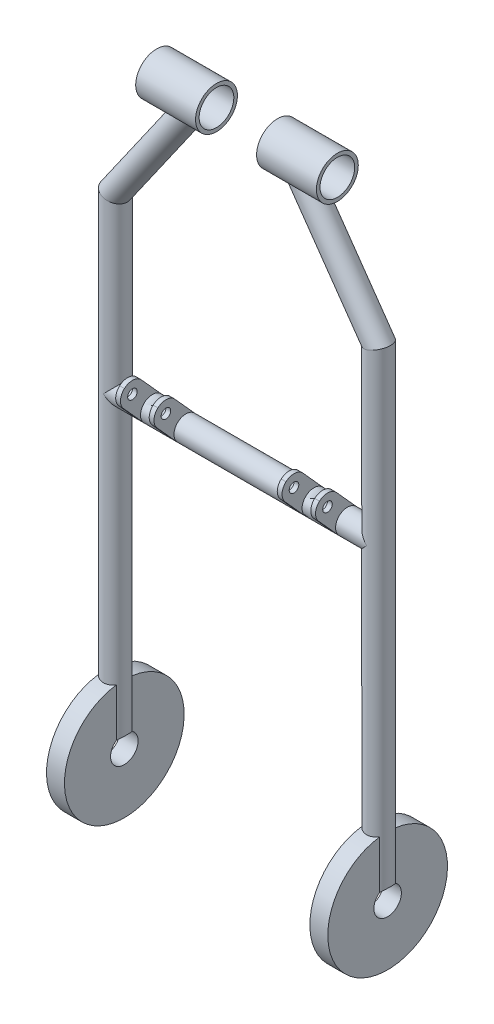
SolidWorks part; units mm, degrees
ref_plane "Alzado" through (0, 0, 0) normal (0, 0, 1) x (1, 0, 0)
ref_plane "Planta" through (0, 0, 0) normal (0, 1, 0) x (1, 0, 0)
ref_plane "Vista lateral" through (0, 0, 0) normal (1, 0, 0) x (0, 0, -1)
sketch "Croquis1" plane through (0, 0, 0) normal (1, 0, 0) x (0, 0, -1)
  circle A0 centre (0, 0) radius 17.5
  circle A1 centre (0, 0) radius 14.5
  dimension "D1" = 35
  dimension "D2" = 3
extrude "Saliente-Extruir1" add sketch "Croquis1" along normal blind 50
sketch "Croquis2" plane through (0, 0, 0) normal (0, 0, 1) x (1, 0, 0)
  line L0 (25, -17.5) -> (-34.5176, -102.5)
  line L1 (-34.5176, -102.5) -> (-34.5176, -502.5)
  line L2 (-34.5176, -102.5) -> (29.5486, -102.5) construction
  line L3 (25, 17.5) -> (25, -17.5) construction
  line L4 (50, 17.5) -> (0, 17.5) construction
  line L5 (0, -17.5) -> (50, -17.5) construction
  line L6 (0, 0) -> (50, 0) construction
  line L7 (50, -17.5) -> (50, 17.5) construction
  dimension "D1" = 85
  dimension "D2" = 400
  dimension "D3" = 55
  dimension "D4" = 64.0663
ref_plane "Plano1" through (25, -17.5, 0) normal (-0.5736, -0.8192, 0) x (0, 0, 1)
sketch "Croquis3" plane through (25, -17.5, 0) normal (-0.5736, -0.8192, 0) x (0, 0, 1)
  circle A0 centre (0, 0) radius 10
  circle A1 centre (0, 0) radius 7
  dimension "D2" = 3
  dimension "D1" = 20
sweep "Barrer1" add profiles "Croquis3" path "Croquis2"
sketch "Croquis4" plane through (50, 0, 0) normal (1, 0, 0) x (0, 0, -1)
  circle A0 centre (0, 0) radius 14.5 construction
  circle A1 centre (0, 0) radius 14.5
extrude "Cortar-Extruir1" cut sketch "Croquis4" against normal through all
sketch "Croquis5" plane through (0.0024, 0.0035, 0) normal (0.5736, 0.8192, 0) x (0.8192, -0.5736, 0)
  arc A4 (40.5164, 0) -> (26.1673, 9.0048) centre (30.5164, 0) ccw
  arc A5 (37.5164, 0) -> (28.2476, 6.6221) centre (30.5164, 0) ccw
  arc A6 (28.2476, -6.6221) -> (37.5164, 0) centre (30.5164, 0) ccw
  arc A7 (26.1673, -9.0048) -> (40.5164, 0) centre (30.5164, 0) ccw
  arc A8 (40.5164, 0) -> (26.1673, 9.0048) centre (30.5164, 0) ccw
  arc A9 (37.5164, 0) -> (28.2476, 6.6221) centre (30.5164, 0) ccw
  arc A10 (28.2476, -6.6221) -> (37.5164, 0) centre (30.5164, 0) ccw
  arc A11 (26.1673, -9.0048) -> (40.5164, 0) centre (30.5164, 0) ccw
  ellipse E2 centre (0.0061, 0) end of major axis (-30.5042, 0) minor radius 17.5 (28.2476, 6.6221) -> (26.1673, 9.0048) ccw
  ellipse E3 centre (0.0061, 0) end of major axis (-30.5042, 0) minor radius 17.5 (26.1673, -9.0048) -> (28.2476, -6.6221) ccw
  ellipse E4 centre (0.0061, 0) end of major axis (-30.5042, 0) minor radius 17.5 (28.2476, 6.6221) -> (26.1673, 9.0048) ccw
  ellipse E5 centre (0.0061, 0) end of major axis (-30.5042, 0) minor radius 17.5 (26.1673, -9.0048) -> (28.2476, -6.6221) ccw
  dimension "D1" = 0
extrude "Saliente-Extruir2" add sketch "Croquis5" along normal up to body separate body
ref_plane "Plano3" through (101, 0, 0) normal (1, 0, 0) x (0, 0, -1)
sketch "Croquis6" plane through (101, 0, 0) normal (1, 0, 0) x (0, 0, -1)
  circle A0 centre (0, 0) radius 14.5 construction
  circle A1 centre (0, 0) radius 17.5 construction
  circle A2 centre (0, 0) radius 14.5
  circle A3 centre (0, 0) radius 17.5
extrude "Saliente-Extruir3" add sketch "Croquis6" along normal blind 50 separate body
sketch "Croquis7" plane through (0, 0, 0) normal (0, 0, 1) x (1, 0, 0)
  line L0 (151, -17.5) -> (151, 17.5) construction
  line L1 (101, -17.5) -> (151, -17.5) construction
  line L2 (101, 17.5) -> (101, -17.5) construction
  line L3 (151, 17.5) -> (101, 17.5) construction
  line L4 (151, -17.5) -> (151, 17.5) construction
  line L5 (101, -17.5) -> (151, -17.5) construction
  line L6 (101, 17.5) -> (101, -17.5) construction
  line L7 (151, 17.5) -> (101, 17.5) construction
  line L8 (126, -17.5) -> (185.5176, -102.5)
  line L9 (185.5176, -102.5) -> (185.5176, -502.5)
  line L10 (185.5176, -102.5) -> (99.3833, -102.5) construction
  dimension "D1" = 85
  dimension "D2" = 400
  dimension "D3" = 86.1343
  dimension "D4" = 55
ref_plane "Plano4" through (126, -17.5, 0) normal (0.5736, -0.8192, 0) x (-0.8192, -0.5736, 0)
sketch "Croquis8" plane through (126, -17.5, 0) normal (0.5736, -0.8192, 0) x (-0.8192, -0.5736, 0)
  circle A0 centre (0, 0) radius 10
  circle A1 centre (0, 0) radius 7
  dimension "D2" = 3
  dimension "D1" = 20
sweep "Barrer2" add profiles "Croquis8" path "Croquis7"
sketch "Croquis9" plane through (49.675, -70.9433, 0) normal (-0.5736, 0.8192, 0) x (0.8192, 0.5736, 0)
  arc A2 (95.4443, 6.6221) -> (95.4443, -6.6221) centre (93.1756, 0) ccw
  arc A3 (97.5246, 9.0048) -> (97.5246, -9.0048) centre (93.1756, 0) ccw
  arc A4 (95.4443, 6.6221) -> (95.4443, -6.6221) centre (93.1756, 0) ccw
  arc A5 (97.5246, 9.0048) -> (97.5246, -9.0048) centre (93.1756, 0) ccw
  ellipse E2 centre (123.6859, 0) end of major axis (93.1756, 0) minor radius 17.5 (97.5246, 9.0048) -> (95.4443, 6.6221) ccw
  ellipse E3 centre (123.6859, 0) end of major axis (93.1756, 0) minor radius 17.5 (95.4443, -6.6221) -> (97.5246, -9.0048) ccw
  ellipse E4 centre (123.6859, 0) end of major axis (93.1756, 0) minor radius 17.5 (97.5246, 9.0048) -> (95.4443, 6.6221) ccw
  ellipse E5 centre (123.6859, 0) end of major axis (93.1756, 0) minor radius 17.5 (95.4443, -6.6221) -> (97.5246, -9.0048) ccw
  dimension "D1" = 0
extrude "Saliente-Extruir4" add sketch "Croquis9" along normal up to surface up to face at (132.5056, -16.5721, 0.0091)
sketch "Croquis10" plane through (0, 0, 0) normal (1, 0, 0) x (0, 0, -1)
  line L0 (10, -102.5) -> (10, -14.3614) construction
  line L1 (-10, -14.3614) -> (-10, -102.5) construction
  line L2 (10, -502.5) -> (10, -102.5) construction
  line L3 (-10, -102.5) -> (-10, -502.5) construction
  line L4 (10, -102.5) -> (10, -14.3614) construction
  line L5 (-10, -14.3614) -> (-10, -102.5) construction
  line L6 (10, -502.5) -> (10, -102.5) construction
  line L7 (-10, -102.5) -> (-10, -502.5) construction
  line L10 (0, -502.5) -> (0, -11.7642) construction
  circle A0 centre (0, -244.3614) radius 10
  dimension "D2" = 20
  dimension "D1" = 230
extrude "Saliente-Extruir5" add sketch "Croquis10" along normal up to surface and the other way up to surface contours A0 up to face at (195.5176, -99.347, 0) other way up to face at (-44.5176, -99.347, 0)
sketch "Croquis11" plane through (0, -502.5, 0) normal (0, -1, 0) x (1, 0, 0)
  line L0 (-34.5176, 0) -> (-44.5176, 0)
  circle A0 centre (-34.5176, 0) radius 10 construction
  circle A1 centre (-34.5176, 0) radius 10 construction
ref_plane "Plano5" through (-34.5176, -502.5, 0) normal (-1, 0, 0) x (0, 0, 1)
sketch "Croquis12" plane through (-34.5176, -502.5, 0) normal (-1, 0, 0) x (0, 0, 1)
  line L0 (-10, 0) -> (10, 0) construction
  circle A0 centre (0, 0) radius 50
  dimension "D1" = 100
extrude "Saliente-Extruir6" add sketch "Croquis12" along normal mid plane 15
chamfer "Chaflán3" distance 7 angle 45 2 edges at (-25.1635, -502.5, -3.5355) (-25.1635, -502.5, 3.5355)
chamfer "Chaflán4" distance 7 angle 45 1 edges at (-44.5176, -502.5, 0)
sketch "Croquis13" plane through (0, -502.5, 0) normal (0, -1, 0) x (1, 0, 0)
  line L0 (185.5176, 0) -> (175.5176, 0) construction
  circle A0 centre (185.5176, 0) radius 10 construction
  circle A1 centre (185.5176, 0) radius 10 construction
ref_plane "Plano6" through (185.5176, -502.5, 0) normal (-1, 0, 0) x (0, 0, 1)
sketch "Croquis14" plane through (185.5176, -502.5, 0) normal (-1, 0, 0) x (0, 0, 1)
  arc A0 (-6.6144, 49.5606) -> (6.6144, 49.5606) centre (0, 0) ccw construction
  arc A1 (-6.6144, 49.5606) -> (6.6144, 49.5606) centre (0, 0) ccw
  circle A2 centre (0, 0) radius 50
extrude "Saliente-Extruir8" add sketch "Croquis14" along normal mid plane 15 contours A2
sketch "Croquis15" plane through (151, 0, 0) normal (1, 0, 0) x (0, 0, -1)
  circle A0 centre (0, 0) radius 14.5 construction
  circle A1 centre (0, 0) radius 14.5
extrude "Cortar-Extruir2" cut sketch "Croquis15" against normal through all contours A1
ref_plane "Plano7" through (75, 0, 0) normal (1, 0, 0) x (0, 0, -1)
sketch "Croquis16" plane through (75, 0, 0) normal (1, 0, 0) x (0, 0, -1)
  line L0 (0, -244.3614) -> (-23.4196, -218.3513)
  line L1 (0, -244.3614) -> (0, -194.3614) construction
  arc A0 (-10, -244.3614) -> (10, -244.3614) centre (0, -244.3614) ccw construction
  arc A1 (10, -244.3614) -> (-10, -244.3614) centre (0, -244.3614) ccw construction
  arc A2 (-10, -244.3614) -> (10, -244.3614) centre (0, -244.3614) ccw
  arc A3 (10, -244.3614) -> (-10, -244.3614) centre (0, -244.3614) ccw
  dimension "D1" = 50
  dimension "D2" = 42
  dimension "D3" = 35
ref_plane "Plano8" through (75, -218.3513, 23.4196) normal (0, 0.7431, 0.6691) x (1, 0, 0)
sketch "Croquis17" plane through (75, -218.3513, 23.4196) normal (0, 0.7431, 0.6691) x (1, 0, 0)
  line L0 (120.5176, -172.7284) -> (120.5176, 97.0336) construction
  line L1 (-119.5176, 97.0336) -> (-119.5176, -168.0445) construction
  line L2 (120.5176, -172.7284) -> (120.5176, 97.0336) construction
  line L3 (-119.5176, 97.0336) -> (-119.5176, -168.0445) construction
  line L4 (-102.8263, -10) -> (103.8263, -10) construction
  line L5 (103.8263, 10) -> (-102.8263, 10) construction
  line L6 (-102.8263, -10) -> (103.8263, -10) construction
  line L7 (103.8263, 10) -> (-102.8263, 10) construction
  line L8 (-119.5176, 0) -> (120.5176, 0) construction
  line L9 (-82.5, 10) -> (-78.5, 10)
  line L10 (-82.5, 10) -> (-82.5, -10)
  line L11 (-82.5, -10) -> (-78.5, -10)
  line L12 (-78.5, 10) -> (-78.5, -10)
  line L13 (-82.5, 10) -> (-78.5, -10) construction
  line L14 (-82.5, -10) -> (-78.5, 10) construction
  line L15 (-50.5, 10) -> (-54.5, 10)
  line L16 (-50.5, 10) -> (-50.5, -10)
  line L17 (-50.5, -10) -> (-54.5, -10)
  line L18 (-54.5, 10) -> (-54.5, -10)
  line L19 (-50.5, 10) -> (-54.5, -10) construction
  line L20 (-50.5, -10) -> (-54.5, 10) construction
  line L29 (0, 0) -> (0, 33.4565) construction
  line L30 (0.5, 0) -> (0.5, -10) construction
  line L31 (0, 0) -> (0, 33.4565) construction
  line L32 (52.5, -10) -> (56.5, -10)
  line L33 (52.5, 10) -> (52.5, -10)
  line L34 (52.5, 10) -> (56.5, 10)
  line L35 (56.5, 10) -> (56.5, -10)
  line L36 (84.5, -10) -> (80.5, -10)
  line L37 (80.5, 10) -> (80.5, -10)
  line L38 (84.5, 10) -> (80.5, 10)
  line L39 (84.5, 10) -> (84.5, -10)
  point P12 (-80.5, 0)
  point P17 (-52.5, 0)
  point P32 (80.5, 10)
  point P33 (0, 0)
  dimension "D1" = 24
  dimension "D2" = 4
  dimension "D3" = 4
  dimension "D4" = 50.5
  dimension "D5" = 52.5
  dimension "D6" = 24
  dimension "D7" = 4
  dimension "D8" = 4
extrude "Saliente-Extruir10" add sketch "Croquis17" against normal up to body separate body contours L12 L11 L10 L9 | L16 L17 L18 L15 | L35 L34 L33 L32 | L36 L37 L38 L39
fillet "Redondeo1" radius 10 8 edges at (157.5, -225.0426, 30.851) (157.5, -211.66, 15.9881) (129.5, -225.0426, 30.851) (129.5, -211.66, 15.9881) (-5.5, -225.0426, 30.851) (-5.5, -211.66, 15.9881) (22.5, -211.66, 15.9881) (22.5, -225.0426, 30.851)
sketch "Croquis18" plane through (-7.5, 0, 0) normal (-1, 0, 0) x (0, 0, 1)
  circle A0 centre (16.7283, -225.7828) radius 4
  dimension "D1" = 8
extrude "Cortar-Extruir3" cut sketch "Croquis18" against normal through all
ref_plane "Plano9" through (-52.0176, 0, 0) normal (-1, 0, 0) x (0, 0, 1)
sketch "Croquis19" plane through (-52.0176, 0, 0) normal (-1, 0, 0) x (0, 0, 1)
  line L0 (-10, -502.5) -> (10, -502.5) construction
  circle A0 centre (0, -502.5) radius 50 construction
  arc A1 (-6.6144, -452.9394) -> (6.6144, -452.9394) centre (0, -502.5) ccw construction
  circle A2 centre (0, -502.5) radius 11.5
  dimension "D1" = 23
extrude "Cortar-Extruir4" cut sketch "Croquis19" against normal through all contours A2
equation "\"Diam_Tubo\"=35"
equation "\"D1@Croquis1\"=\"Diam_Tubo\""
equation "\"Grosor_Tubo\"=3"
equation "\"D2@Croquis1\"=\"Grosor_Tubo\""
equation "\"Dist_Sec\"=85"
equation "\"D1@Croquis2\"=\"Dist_Sec\""
equation "\"Diste_sec\" = 400"
equation "\"D2@Croquis2\"=\"Diste_sec\""
equation "\"Inclinacion_Princ\"= 55"
equation "\"D3@Croquis2\"=\"Inclinacion_Princ\""
equation "\"D2@Croquis3\"=\"Grosor_Tubo\""
equation "\"Diam_Tubo2\"=20"
equation "\"D1@Croquis3\"=\"Diam_Tubo2\""
equation "\"Ext_Tubo\"= 50"
equation "\"D1@Saliente-Extruir1\"=\"Ext_Tubo\""
equation "\"D1@Saliente-Extruir3\"=\"Ext_Tubo\""
equation "\"D1@Croquis7\"=\"Dist_Sec\""
equation "\"D2@Croquis7\"=\"Diste_sec\""
equation "\"D4@Croquis7\"=\"Inclinacion_Princ\""
equation "\"D1@Croquis8\"=\"Diam_Tubo2\""
equation "\"D2@Croquis8\"=\"Grosor_Tubo\""
equation "\"Dist_Soporte_Amortiguador\" = 230"
equation "\"D2@Croquis10\"=\"Diam_Tubo2\""
equation "\"Ext_Sop_Rueda\"= 15"
equation "\"D1@Saliente-Extruir6\"=\"Ext_Sop_Rueda\""
equation "\"Tubo_Rueda\"= 100"
equation "\"D1@Saliente-Extruir8\"=\"Ext_Sop_Rueda\""
equation "\"Ang_Perp_SopAmort\" = 42"
equation "\"D2@Croquis16\"=\"Ang_Perp_SopAmort\""
equation "\"Largo_SopAmort\"= 35"
equation "\"D3@Croquis16\"=\"Largo_SopAmort\""
equation "\"Dist_Entre_SopAmort\"= 24"
equation "\"D1@Croquis17\"=\"Dist_Entre_SopAmort\""
equation "\"Grosor_SopAmort\"=4"
equation "\"D2@Croquis17\"=\"Grosor_SopAmort\""
equation "\"D3@Croquis17\"=\"Grosor_SopAmort\""
equation "\"Dist_SopRu_SopAmort\"=36.881"
equation "\"Agujero_Amort\"=8"
equation "\"D1@Croquis10\"=\"Dist_Soporte_Amortiguador\""
equation "\"D1@Croquis12\"=\"Tubo_Rueda\""
equation "\"D1@Croquis18\"=\"Agujero_Amort\""
equation "\"D6@Croquis17\"=\"D1@Croquis17\""
equation "\"D7@Croquis17\"=\"D3@Croquis17\""
equation "\"D8@Croquis17\"=\"D3@Croquis17\""
equation "\"Entrada_Eje\"=23"
equation "\"D1@Croquis19\"=\"Entrada_Eje\""
